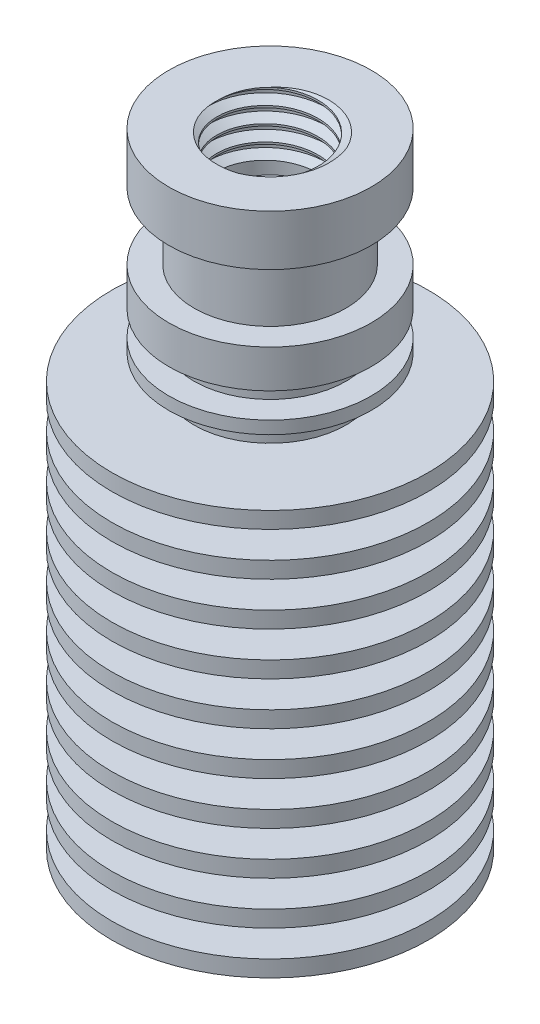
SolidWorks part; units mm, degrees
material "1060-H12"
ref_plane "Front Plane" through (0, 0, 0) normal (0, 0, 1) x (1, 0, 0)
ref_plane "Top Plane" through (0, 0, 0) normal (0, 1, 0) x (1, 0, 0)
ref_plane "Right Plane" through (0, 0, 0) normal (1, 0, 0) x (0, 0, -1)
sketch "Sketch1" plane through (0, 0, 0) normal (0, 0, 1) x (1, 0, 0)
  line L0 (0, 5.3884) -> (0, -80.016) construction
  line L1 (6, -9.3) -> (8, -9.3)
  line L2 (4, 0) -> (8, 0)
  line L3 (8, 0) -> (8, -4)
  line L4 (8, -4) -> (6, -4)
  line L5 (6, -4) -> (6, -9.3)
  line L6 (8, -9.3) -> (8, -12.3)
  line L7 (8, -12.3) -> (6, -12.3)
  line L8 (6, -12.3) -> (6, -14.3)
  line L9 (6, -14.3) -> (8, -14.3)
  line L10 (8, -14.3) -> (8, -15.3)
  line L11 (8, -15.3) -> (6, -15.3)
  line L12 (1, -8) -> (1, -25.3)
  line L13 (6, -15.3) -> (6, -17.3)
  line L14 (6, -17.3) -> (12.5, -17.3)
  line L15 (12.5, -17.3) -> (12.5, -18.6)
  line L16 (12.5, -18.6) -> (7.5, -18.6)
  line L17 (7.5, -18.6) -> (7.5, -20.7111)
  line L18 (7.5, -20.7111) -> (12.5, -20.7111)
  line L19 (12.5, -20.7111) -> (12.5, -22.0111)
  line L20 (12.5, -22.0111) -> (7.5, -22.0111)
  line L21 (7.5, -22.0111) -> (7.5, -24.1222)
  line L22 (7.5, -24.1222) -> (12.5, -24.1222)
  line L23 (12.5, -24.1222) -> (12.5, -25.4222)
  line L24 (12.5, -25.4222) -> (7.5, -25.4222)
  line L25 (7.5, -25.4222) -> (7.5, -27.5333)
  line L26 (7.5, -27.5333) -> (12.5, -27.5333)
  line L27 (12.5, -27.5333) -> (12.5, -28.8333)
  line L28 (12.5, -28.8333) -> (7.5, -28.8333)
  line L29 (7.5, -28.8333) -> (7.5, -30.9444)
  line L30 (7.5, -30.9444) -> (12.5, -30.9444)
  line L31 (12.5, -30.9444) -> (12.5, -32.2444)
  line L32 (12.5, -32.2444) -> (7.5, -32.2444)
  line L33 (7.5, -41.1778) -> (12.5, -41.1778)
  line L34 (12.5, -34.3556) -> (12.5, -35.6556)
  line L35 (12.5, -35.6556) -> (7.5, -35.6556)
  line L36 (12.5, -39.0667) -> (7.5, -39.0667)
  line L37 (12.5, -37.7667) -> (12.5, -39.0667)
  line L38 (12.5, -44.5889) -> (12.5, -45.8889)
  line L39 (7.5, -37.7667) -> (12.5, -37.7667)
  line L40 (7.5, -42.4778) -> (7.5, -44.5889)
  line L41 (7.5, -44.5889) -> (12.5, -44.5889)
  line L42 (12.5, -41.1778) -> (12.5, -42.4778)
  line L43 (12.5, -48) -> (12.5, -49.3)
  line L44 (12.5, -45.8889) -> (7.5, -45.8889)
  line L45 (7.5, -48) -> (12.5, -48)
  line L46 (12.5, -49.3) -> (3, -49.3)
  line L47 (7.5, -35.6556) -> (7.5, -37.7667)
  line L48 (7.5, -45.8889) -> (7.5, -48)
  line L49 (7.5, -39.0667) -> (7.5, -41.1778)
  line L50 (12.5, -42.4778) -> (7.5, -42.4778)
  line L51 (7.5, -32.2444) -> (7.5, -34.3556)
  line L52 (7.5, -34.3556) -> (12.5, -34.3556)
  line L53 (3, -49.3) -> (3, -25.3)
  line L54 (3, -25.3) -> (1, -25.3)
  line L55 (4, 0) -> (4, -6)
  line L56 (4, -6) -> (1, -8)
  dimension "D1" = 3
  dimension "D2" = 8
  dimension "D3" = 6
  dimension "D4" = 5.3
  dimension "D5" = 4
  dimension "D6" = 2
  dimension "D7" = 1
  dimension "D8" = 1
  dimension "D9" = 2
  dimension "D10" = 32
  dimension "D11" = 1.3
  dimension "D12" = 12.5
  dimension "D13" = 5
  dimension "D14" = 24
  dimension "D15" = 3
  dimension "D16" = 8
  dimension "D17" = 6
  dimension "D18" = 8
revolve "Revolve1" add sketch "Sketch1" angle 360 about L0
thread "Thread1" pitch 1 method cut profile "Thread Profile1" start angle 0, offset 1, length 25, pitch 1, diameter 6
ref_plane "Plane1" through (3, -50.3, 0) normal (0, 0, 1) x (1, 0, 0)
sketch "Thread Profile1" plane through (3, -50.3, 0) normal (0, 0, 1) x (1, 0, 0)
  line L0 (0, 0) -> (0, 1) construction
  line L11 (0, 0.875) -> (0, 0)
  line L12 (0, 0) -> (0.5413, 0.3125)
  line L13 (0.5413, 0.3125) -> (0.5413, 0.5625)
  line L15 (0.5413, 0.5625) -> (0, 0.875)
  line L17 (0.5413, 0.4375) -> (0, 0.4375) construction
  point P3 (0, 0)
  dimension "Pitch" = 1
  dimension "Profile_Angle" = 60
  dimension "Profile_Land" = 0.25
  dimension "Profile_Height" = 0.5413
thread "Thread2" pitch 1.25 method cut profile "Thread Profile3" start angle 0, offset 1.25, length 6, pitch 1.25, diameter 8
ref_plane "Plane3" through (-4, 1.25, 0) normal (0, 0, 1) x (-1, 0, 0)
sketch "Thread Profile3" plane through (-4, 1.25, 0) normal (0, 0, 1) x (-1, 0, 0)
  line L0 (0, 0) -> (0, 1.25) construction
  line L11 (0, 1.0938) -> (0, 0)
  line L12 (0, 0) -> (0.6766, 0.3906)
  line L13 (0.6766, 0.3906) -> (0.6766, 0.7031)
  line L15 (0.6766, 0.7031) -> (0, 1.0938)
  line L17 (0.6766, 0.5469) -> (0, 0.5469) construction
  point P3 (0, 0)
  dimension "Pitch" = 1.25
  dimension "Profile_Angle" = 60
  dimension "Profile_Land" = 0.3125
  dimension "Profile_Height" = 0.6766
